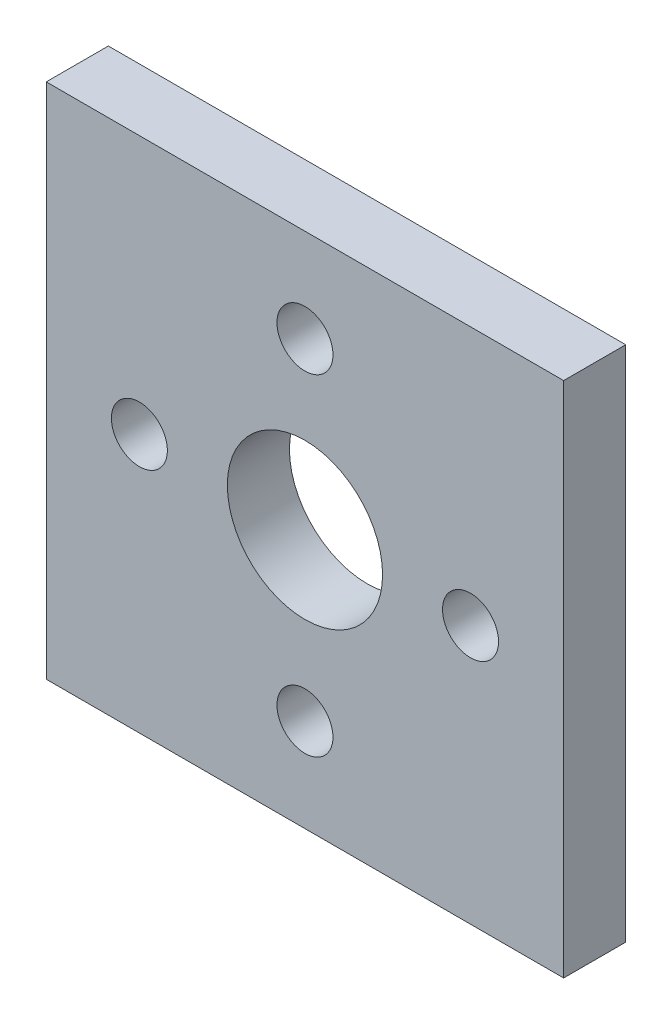
SolidWorks part; units mm, degrees
ref_plane "Front" through (0, 0, 0) normal (0, 0, 1) x (1, 0, 0)
ref_plane "Top" through (0, 0, 0) normal (0, 1, 0) x (1, 0, 0)
ref_plane "Right" through (0, 0, 0) normal (1, 0, 0) x (0, 0, -1)
ref_axis "side-side" through (80.9, 0, 0) along (-1, 0, 0)
ref_axis "up-down" through (0, 50, 0) along (0, -1, 0)
ref_axis "front-back" through (0, 0, -80.9) along (0, 0, 1)
sketch "Sketch1" plane through (0, 0, 0) normal (0, 0, 1) x (1, 0, 0)
  line L0 (-12.5, 12.5) -> (12.5, -12.5) construction
  line L1 (-12.5, 12.5) -> (12.5, 12.5)
  line L2 (-12.5, 12.5) -> (-12.5, -12.5)
  line L3 (-12.5, -12.5) -> (12.5, -12.5)
  line L4 (12.5, 12.5) -> (12.5, -12.5)
  line L5 (0, 0) -> (8, 0) construction
  line L6 (0, 0) -> (0, 8) construction
  line L7 (0, 0) -> (-8, 0) construction
  line L8 (0, 0) -> (0, -8) construction
  circle A0 centre (0, 0) radius 3.75
  circle A1 centre (0, 8) radius 1.3525
  circle A2 centre (0, -8) radius 1.3526
  circle A3 centre (8, 0) radius 1.3526
  circle A4 centre (-8, 0) radius 1.3526
  dimension "D2" = 7.5
  dimension "D4" = 2.7051
  dimension "D1" = 25
  dimension "D3" = 8
extrude "Boss-Extrude1" add sketch "Sketch1" along normal blind 3
